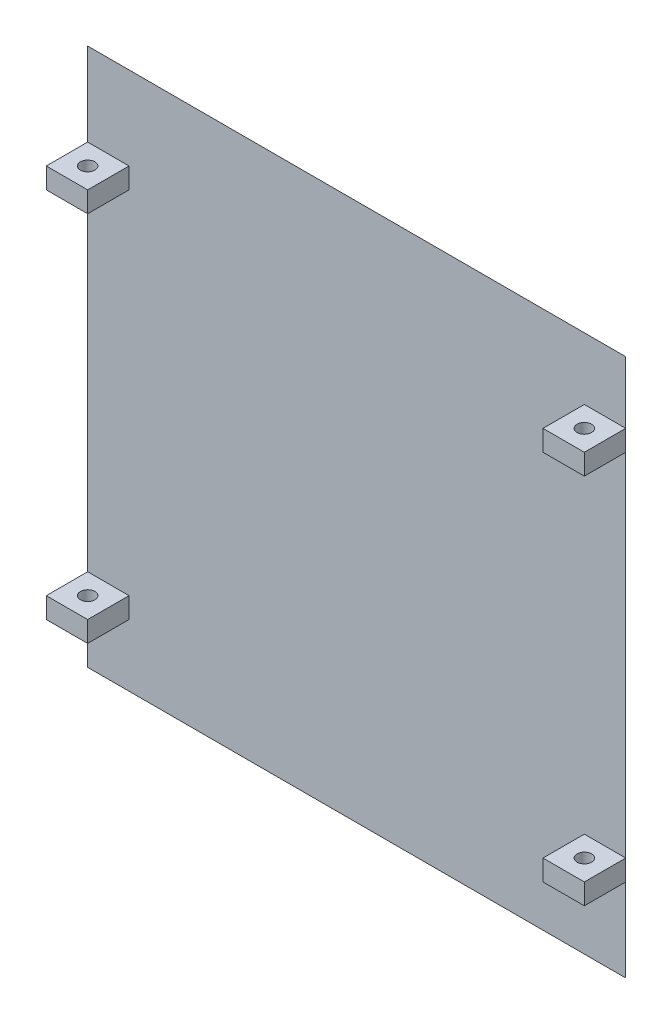
SolidWorks part; units mm, degrees
ref_plane "Plan de face" through (0, 0, 0) normal (0, 0, 1) x (1, 0, 0)
ref_plane "Plan de dessus" through (0, 0, 0) normal (0, 1, 0) x (1, 0, 0)
ref_plane "Plan de droite" through (0, 0, 0) normal (1, 0, 0) x (0, 0, -1)
sketch "Esquisse1" plane through (0, 0, 0) normal (0, 0, 1) x (1, 0, 0)
  line L1 (0, 130) -> (130, 130)
  line L2 (0, 130) -> (0, 0)
  line L3 (0, 0) -> (130, 0)
  line L4 (130, 130) -> (130, 0)
  dimension "D1" = 130
  dimension "D2" = 130
extrude "Boss.-Extru.1" add sketch "Esquisse1" along normal blind 3
chamfer "Chanfrein1" distance 3 angle 45 4 edges at (65, 130, 0) (130, 65, 0) (65, 0, 0) (0, 65, 0)
sketch "Esquisse2" plane through (0, 0, 3) normal (0, 0, 1) x (1, 0, 0)
  line L0 (0, 109.9) -> (10, 109.9)
  line L1 (0, 20) -> (10, 20)
  line L2 (0, 20) -> (0, 15)
  line L3 (0, 15) -> (10, 15)
  line L4 (10, 20) -> (10, 15)
  line L5 (0, 109.9) -> (0, 104.9)
  line L6 (130, 20.1) -> (120, 20.1)
  line L7 (130, 20.1) -> (130, 25.1)
  line L8 (130, 25.1) -> (120, 25.1)
  line L9 (120, 20.1) -> (120, 25.1)
  line L10 (0, 104.9) -> (10, 104.9)
  line L11 (0, 0) -> (130, 0) construction
  line L12 (10, 109.9) -> (10, 104.9)
  line L13 (130, 110) -> (120, 110)
  line L14 (130, 110) -> (130, 115)
  line L15 (130, 115) -> (120, 115)
  line L16 (120, 110) -> (120, 115)
  line L17 (130, 0) -> (130, 130) construction
  line L18 (0, 130) -> (0, 0) construction
  line L19 (130, 130) -> (0, 130) construction
  dimension "D1" = 10
  dimension "D2" = 5
  dimension "D3" = 5
  dimension "D4" = 10
  dimension "D5" = 20.1
  dimension "D6" = 15
  dimension "D7" = 10
  dimension "D8" = 5
  dimension "D9" = 5
  dimension "D10" = 10
  dimension "D11" = 20.1
  dimension "D12" = 15
extrude "Boss.-Extru.2" add sketch "Esquisse2" along normal blind 10
sketch "Esquisse4" plane through (0, 15, 0) normal (0, -1, 0) x (1, 0, 0)
  circle A0 centre (5, 8) radius 1.75
  dimension "D1" = 3.5
extrude "Enlèv. mat.-Extru.1" cut sketch "Esquisse4" against normal through all
sketch "Esquisse5" plane through (0, 20.1, 0) normal (0, -1, 0) x (1, 0, 0)
  circle A0 centre (125, 8) radius 1.75
  dimension "D1" = 3.5
extrude "Enlèv. mat.-Extru.2" cut sketch "Esquisse5" against normal through all
